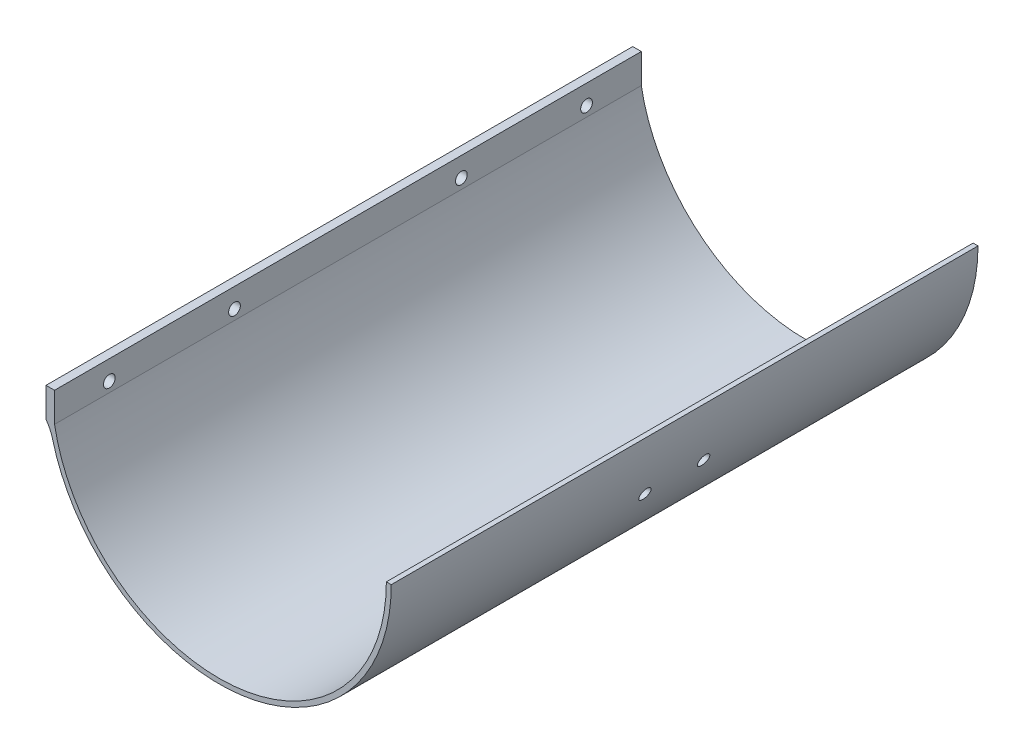
SolidWorks part; units mm, degrees
ref_plane "Front Plane" through (0, 0, 0) normal (0, 0, 1) x (1, 0, 0)
ref_plane "Top Plane" through (0, 0, 0) normal (0, 1, 0) x (1, 0, 0)
ref_plane "Right Plane" through (0, 0, 0) normal (1, 0, 0) x (0, 0, -1)
sketch "Sketch1" plane through (0, 0, 0) normal (0, 0, 1) x (1, 0, 0)
  line L0 (-44, 0) -> (-42.75, 0)
  line L1 (42.75, 0) -> (44, 0)
  arc A0 (-44, 0) -> (44, 0) centre (0, 0) ccw
  arc A1 (-42.75, 0) -> (42.75, 0) centre (0, 0) ccw
  dimension "D1" = 88
  dimension "D2" = 85.5
extrude "Boss-Extrude1" add sketch "Sketch1" along normal blind 150
sketch "Sketch2" plane through (0, 0, 0) normal (1, 0, 0) x (0, 0, -1)
  line L2 (-150, 0) -> (0, 0) construction
  line L3 (-150, 0) -> (-150, -44) construction
  circle A0 centre (-136, -5) radius 1.5
  circle A1 centre (-104, -5) radius 1.5
  circle A2 centre (-46, -5) radius 1.5
  circle A3 centre (-14, -5) radius 1.5
  dimension "D1" = 3
  dimension "D2" = 3
  dimension "D3" = 3
  dimension "D4" = 3
  dimension "D5" = 32
  dimension "D6" = 32
  dimension "D7" = 58
  dimension "D8" = 14
  dimension "D10" = 5
extrude "Cut-Extrude1" cut sketch "Sketch2" against normal up to surface (43.715 mm away) up to face at (0, -22, 75)
ref_plane "Plane1" through (0, 0, 72) normal (0, 0, -1) x (-1, 0, 0)
sketch "Sketch4" plane through (0, 0, 72) normal (0, 0, -1) x (-1, 0, 0)
  line L0 (-42.1884, 12.4954) -> (-40.8831, 12.4954)
  line L1 (-44, 0) -> (-42.75, 0)
  arc A0 (-40.8831, 12.4954) -> (-42.75, 0) centre (0, 0) ccw
  arc A1 (-42.1884, 12.4954) -> (-44, 0) centre (0, 0) ccw
  dimension "D1" = 88
  dimension "D2" = 85.5
extrude "Boss-Extrude2" add sketch "Sketch4" along normal blind 7.5 and the other way blind 7.5
sketch "Sketch5" plane through (0, 0, 150) normal (0, 0, 1) x (1, 0, 0)
  line L5 (-44, 0) -> (-44, -7.5543)
  line L6 (-44, -7.5543) -> (-42.7628, -7.5543)
  line L7 (-42.7628, -7.5543) -> (-42.7628, 0)
  line L8 (-42.75, 0) -> (-44, 0) construction
  line L9 (-42.7628, 0) -> (-44, 0)
extrude "Cut-Extrude2" cut sketch "Sketch5" against normal up to surface (150 mm away) up to face at (0, -21.6875, 0)
sketch "Sketch6" plane through (-42.7628, 0, 0) normal (-1, 0, 0) x (0, 0, 1)
  line L1 (0, -7.5543) -> (150, -7.5543)
  line L2 (0, -7.5543) -> (0, 0)
  line L3 (0, 0) -> (150, 0)
  line L4 (150, -7.5543) -> (150, 0)
  circle A0 centre (14, -5) radius 1.5
  circle A1 centre (46, -5) radius 1.5
  circle A2 centre (104, -5) radius 1.5
  circle A3 centre (136, -5) radius 1.5
  circle M5 centre (46, -5) radius 1.5
  circle M6 centre (136, -5) radius 1.5
  line M7 (0, 0) -> (0, -7.5543)
  line M8 (0, -7.5543) -> (150, -7.5543)
  line M9 (150, -7.5543) -> (150, 0)
  line M10 (150, 0) -> (0, 0)
  circle M11 centre (104, -5) radius 1.5
  circle M12 centre (14, -5) radius 1.5
extrude "Boss-Extrude3" add sketch "Sketch6" along normal blind 0.5 contours M10 M7 M8 M9 M6 M11 M12 M5 region at (-42.7628, -3.7459, 75)
sketch "Sketch7" plane through (0, 0, 150) normal (0, 0, 1) x (1, 0, 0)
  line L0 (3.1936, -47.2716) -> (4.2473, -46.1824)
  line L2 (2.6526, -44.3202) -> (7.0646, -42.9225)
  line L3 (2.6526, -44.3202) -> (-0.0812, -45.0066)
  line L4 (-2.6526, -44.3202) -> (-7.0646, -42.9225)
  arc A1 (-0.0812, -45.0066) -> (3.1936, -47.2716) centre (-0.0812, -48.5066) ccw
  arc A2 (-2.6526, -44.3202) -> (4.2473, -46.1824) centre (-0.0812, -48.5066) ccw
  arc A3 (-7.0646, -42.9225) -> (7.0646, -42.9225) centre (0, 0) ccw
  dimension "D1" = 43.5
  dimension "D2" = 7
extrude "Boss-Extrude4" add sketch "Sketch7" against normal blind 80
fillet "Fillet3" radius 0.5 1 edges at (4.2473, -46.1824, 110)
sketch "Sketch9" plane through (0, 0, 0) normal (1, 0, 0) x (0, 0, -1)
  line L0 (-79.5, 12.4954) -> (-79.5, 0) construction
  line L1 (-78, 8.4954) -> (-66, 8.4954)
  line L2 (-78, 8.4954) -> (-78, 2.4954)
  line L3 (-78, 2.4954) -> (-66, 2.4954)
  line L4 (-66, 8.4954) -> (-66, 2.4954)
  line L5 (-79.5, 12.4954) -> (-64.5, 12.4954) construction
  dimension "D1" = 12
  dimension "D2" = 6
  dimension "D3" = 1.5
  dimension "D4" = 4
extrude "Cut-Extrude4" cut sketch "Sketch9" along normal up to surface (43.1721 mm away) up to face at (15.0324, -18.3013, 85.6667)
sketch "Sketch11" plane through (0, 0, 150) normal (0, 0, 1) x (1, 0, 0)
  line L1 (6.0382, -53.7585) -> (4.3409, -43.7853)
  line L2 (6.0382, -53.7585) -> (2.0015, -51.3196)
  line L3 (-6.6638, -46.7537) -> (-4.3409, -43.7853)
  line L4 (2.6526, -44.3202) -> (4.3409, -43.7853) construction
  arc A1 (-6.6638, -46.7537) -> (6.0382, -53.7585) centre (2.0015, -46.0596) ccw
  arc A2 (-4.3409, -43.7853) -> (4.3409, -43.7853) centre (0, 0) ccw
  arc A3 (-0.0812, -45.0066) -> (3.1936, -47.2716) centre (-0.0812, -48.5066) ccw construction
  arc A4 (4.3409, -43.7853) -> (44, 0) centre (0, 0) ccw construction
  dimension "D1" = 44
extrude "Cut-Extrude5" cut sketch "Sketch11" against normal blind 67 contours A1 L3 A2 L1
sketch "Sketch12" plane through (0, 0, 0) normal (0, 0, -1) x (-1, 0, 0)
  line L2 (42.75, 0) -> (42.75, -7.5543)
  line L6 (42.75, -7.5543) -> (41.523, -7.5543)
  line L7 (41.523, -7.5543) -> (42.75, 0)
extrude "Cut-Extrude6" cut sketch "Sketch12" against normal up to surface (150 mm away) up to face at (-13.7346, -16.3196, 150)
sketch "Sketch14" plane through (-43.2628, 0, 0) normal (-1, 0, 0) x (0, 0, 1)
  line L0 (0, -7.5543) -> (150, -7.5543) construction
  line L1 (0, 0) -> (150, 0)
  line L2 (0, 0) -> (0, -7.5543)
  line L3 (0, -7.5543) -> (150, -7.5543)
  line L4 (150, 0) -> (150, -7.5543)
  line L5 (150, -7.5543) -> (150, 0) construction
  circle A0 centre (14, -5) radius 1.5
  circle A1 centre (46, -5) radius 1.5
  circle A2 centre (104, -5) radius 1.5
  circle A3 centre (136, -5) radius 1.5
extrude "Boss-Extrude5" add sketch "Sketch14" along normal blind 1 and the other way blind 1.5
sketch "Sketch17" plane through (0, -7.5543, 0) normal (0, -1, 0) x (1, 0, 0)
  line L1 (-42.0773, 150) -> (-41.7628, 150)
  line L2 (-42.0773, 150) -> (-42.0773, 0)
  line L3 (-42.0773, 0) -> (-41.7628, 0)
  line L4 (-41.7628, 150) -> (-41.7628, 0)
extrude "Cut-Extrude8" cut sketch "Sketch17" against normal up to surface (7.5543 mm away) up to face at (-43.0128, 0, 75)
fillet "Fillet4" radius 10 1 edges at (-43.3467, -7.5543, 75)
sketch "Sketch18" plane through (0, 0, 79.5) normal (0, 0, 1) x (1, 0, 0)
  line L1 (40.1344, 0) -> (45.8139, 0)
  line L2 (40.1344, 0) -> (40.1344, 15.0548)
  line L3 (40.1344, 15.0548) -> (45.8139, 15.0548)
  line L4 (45.8139, 0) -> (45.8139, 15.0548)
extrude "Cut-Extrude9" cut sketch "Sketch18" against normal up to surface (15 mm away) up to face at (42.6841, 6.2814, 64.5)
sketch "Sketch19" plane through (-42.0773, 0, 0) normal (1, 0, 0) x (0, 0, -1)
  line L0 (-75, 0) -> (-75, -20.7313) construction
  line L1 (-150, 0) -> (0, 0) construction
  circle A0 centre (-82.5, -15) radius 1.5
  circle A1 centre (-67.5, -15) radius 1.5
  dimension "D1" = 3
  dimension "D2" = 3
  dimension "D3" = 15
  dimension "D4" = 7.5
  dimension "D5" = 15
extrude "Cut-Extrude10" cut sketch "Sketch19" along normal up to surface (63.4415 mm away) from offset 20 up to face at (3.1311, -24.5812, 75)
sketch "Sketch20" plane through (0, 0, 70) normal (0, 0, -1) x (-1, 0, 0)
  line L0 (4.2376, -51.1264) -> (9.3647, -42.9919)
  line L1 (2.6526, -44.3202) -> (4.3409, -43.7853)
  arc A0 (4.2376, -51.1264) -> (2.6526, -44.3202) centre (0.0812, -48.5066) ccw
  arc A3 (-44, 0) -> (42.595, -11.0303) centre (0, 0) ccw construction
  arc A4 (4.3409, -43.7853) -> (9.3647, -42.9919) centre (0, 0) ccw
  arc A5 (-4.5622, -46.9012) -> (2.6526, -44.3202) centre (0.0812, -48.5066) ccw construction
extrude "Boss-Extrude6" add sketch "Sketch20" against normal up to surface (13 mm away) up to face at (0.6422, -46.8572, 83)
